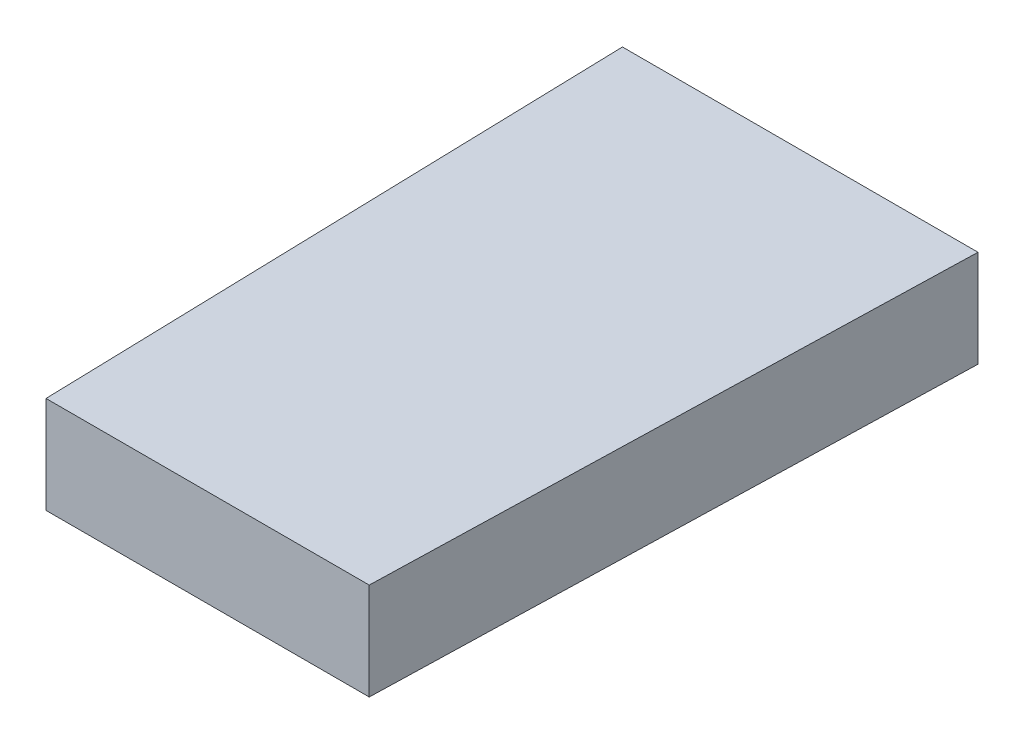
SolidWorks part; units mm, degrees
ref_plane "Front" through (0, 0, 0) normal (0, 0, 1) x (1, 0, 0)
ref_plane "Top" through (0, 0, 0) normal (0, 1, 0) x (1, 0, 0)
ref_plane "Right" through (0, 0, 0) normal (1, 0, 0) x (0, 0, -1)
ref_axis "X" through (-80.9, 0, 0) along (1, 0, 0)
ref_axis "Y" through (0, -50, 0) along (0, 1, 0)
ref_axis "Z" through (0, 0, -80.9) along (0, 0, 1)
sketch "Sketch1" plane through (0, 0, 0) normal (0, 1, 0) x (1, 0, 0)
  line L0 (-16.5, 27.5) -> (-15, -27.5)
  line L1 (-15, -27.5) -> (15, -27.5)
  line L2 (15, -27.5) -> (16.5, 27.5)
  line L3 (16.5, 27.5) -> (-16.5, 27.5)
  line L4 (0, -27.5) -> (0, 0) construction
  line L5 (0, 0) -> (0, 27.5) construction
  dimension "D1" = 33
  dimension "D2" = 30
  dimension "D3" = 55
extrude "Boss-Extrude1" add sketch "Sketch1" along normal mid plane 9
